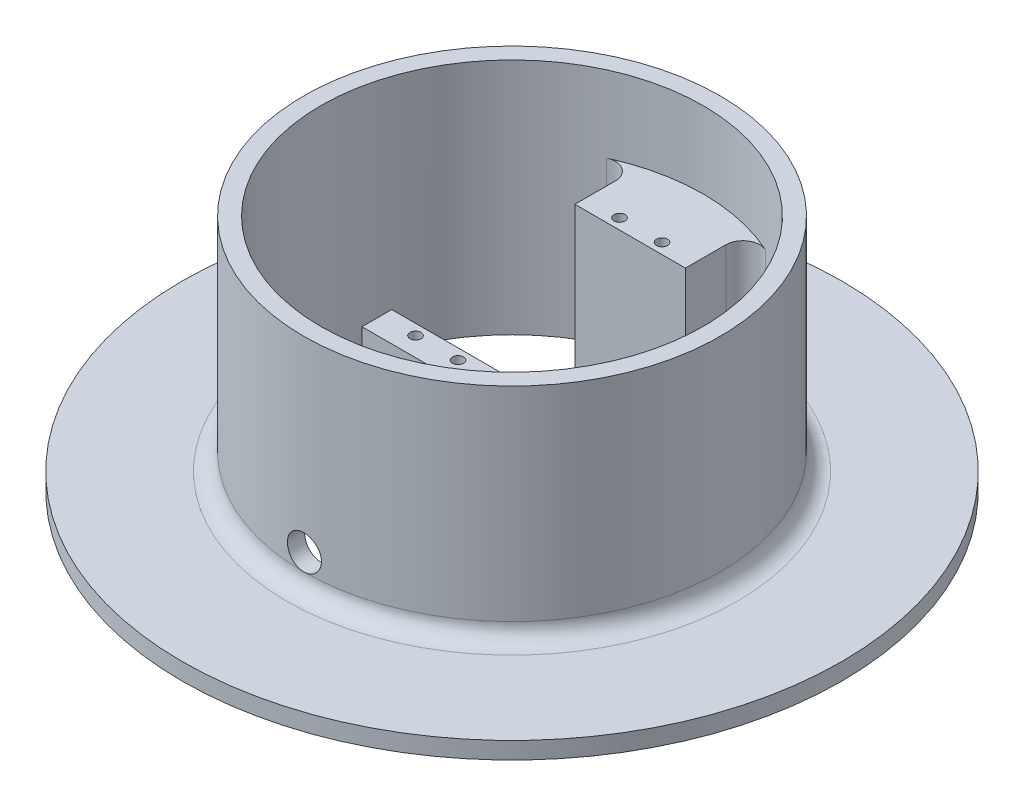
SolidWorks part; units mm, degrees
ref_plane "Front Plane" through (0, 0, 0) normal (0, 0, 1) x (1, 0, 0)
ref_plane "Top Plane" through (0, 0, 0) normal (0, 1, 0) x (1, 0, 0)
ref_plane "Right Plane" through (0, 0, 0) normal (1, 0, 0) x (0, 0, -1)
sketch "Croquis1" plane through (0, 0, 0) normal (0, 1, 0) x (1, 0, 0)
  line L0 (-10, -24.2) -> (-23.9176, -38.1176)
  line L1 (0, -45) -> (0, -24.2)
  line L2 (0, -24.2) -> (-10, -24.2)
  line L3 (0, -24.2) -> (10, -24.2)
  line L7 (0, -24.2) -> (0, -15.2)
  line L8 (0, -15.2) -> (-13.1, -15.2)
  line L9 (0, -15.2) -> (13.1, -15.2)
  line L11 (-13.1, -15.2) -> (-30.7525, -32.8525)
  line L12 (13.1, -15.2) -> (30.7525, -32.8525)
  line L13 (10, -24.2) -> (23.9176, -38.1176)
  arc A1 (-13.3684, -42.9684) -> (23.9176, -38.1176) centre (0, 0) ccw
  arc A2 (40.095, -20.4301) -> (-30.7525, -32.8525) centre (0, 0) ccw
  arc A3 (-23.9176, -38.1176) -> (23.9176, -38.1176) centre (0, 0) ccw
  arc A4 (-23.9176, -38.1176) -> (-18.1343, -41.1843) centre (0, 0) ccw
  arc A5 (30.7525, -32.8525) -> (34.7133, -28.6354) centre (0, 0) ccw
  arc A6 (30.7525, -32.8525) -> (-30.7525, -32.8525) centre (0, 0) ccw
  circle A7 centre (0, 0) radius 77.5745
  dimension "D1" = 90
  dimension "D2" = 20.8
  dimension "D3" = 10
  dimension "D4" = 10
  dimension "D6" = 9
  dimension "D7" = 13.1
  dimension "D8" = 13.1
sketch "Croquis3" plane through (0, 0, 0) normal (0, 1, 0) x (1, 0, 0)
  circle A0 centre (0, 0) radius 45
  circle A1 centre (0, 0) radius 49
  dimension "D1" = 90
  dimension "D2" = 98
extrude "Saliente-Extruir1" add sketch "Croquis3" along normal blind 56
extrude "Saliente-Extruir2" add sketch "Croquis1" along normal blind 4 contours A2 L9 L3 A1 L2 L8 region at (-75.3804, 0, 0)
sketch "Croquis5" plane through (0, 0, 0) normal (0, 1, 0) x (1, 0, 0)
  line L0 (0, -15.2) -> (0, 27.8)
  line L1 (-13.1, -15.2) -> (13.1, -15.2) construction
  line L2 (0, 27.8) -> (-13, 27.8)
  line L3 (0, 27.8) -> (13, 27.8)
  line L4 (-13, 27.8) -> (-13, 37.3095)
  line L5 (13, 27.8) -> (13, 37.3095)
  line L6 (-13.1, -15.2) -> (-13.1, -22.2)
  line L7 (-13.1, -22.2) -> (13, -22.2)
  line L8 (13, -22.2) -> (13.1, -15.2)
  line L10 (-13.1, -15.2) -> (13.1, -15.2)
  circle A0 centre (0, 0) radius 45 construction
  arc A2 (18.6585, 40.9495) -> (13, 37.3095) centre (17, 37.3095) ccw
  arc A3 (-18.6585, 40.9495) -> (-13, 37.3095) centre (-17, 37.3095) cw
  arc A4 (18.6585, 40.9495) -> (-18.6585, 40.9495) centre (0, 0) ccw
  point P14 (13, 43.0813)
  point P17 (-13, 43.0813)
  dimension "D4" = 4
  dimension "D1" = 43
  dimension "D2" = 13
  dimension "D3" = 13
  dimension "D5" = 7
extrude "Saliente-Extruir3" add sketch "Croquis5" along normal blind 38 contours A2 A4 A3 L4 L2 L3 L5 | L10 L6 L7 L8 region at (0, 0, -36.2791) region at (-0.025, 0, 18.6978)
ref_plane "Plano1" through (0, 0, 15) normal (0, 0, 1) x (1, 0, 0)
sketch "Croquis6" plane through (0, 0, 15) normal (0, 0, 1) x (1, 0, 0)
  line L0 (0, 0) -> (0, 5)
  line L1 (0, 5) -> (-5, 5)
  line L2 (-5, 5) -> (-5, 29)
  line L3 (-5, 29) -> (-2.4928, 29)
  line L4 (-2.4928, 29) -> (5, 29)
  line L5 (5, 29) -> (5, 5)
  line L6 (5, 5) -> (0, 5)
  dimension "D1" = 5
  dimension "D2" = 5
  dimension "D3" = 5
  dimension "D4" = 24
  dimension "D5" = 24
extrude "Cortar-Extruir1" cut sketch "Croquis6" along normal blind 8 contours L6 L5 L4 L3 L2 L1 region at (0, 17, 15)
sketch "Croquis7" plane through (0, 0, 15) normal (0, 0, 1) x (1, 0, 0)
  line L0 (0, 0) -> (0, 12)
  circle A0 centre (0, 12) radius 4
  dimension "D1" = 12
extrude "Cortar-Extruir2" cut sketch "Croquis7" along normal blind 42 contours A0 region at (2.7484, 9.2516, 15)
fillet "Redondeo1" radius 4 1 edges at (0, 4, 49)
fillet "Redondeo2" radius 1 3 edges at (-0.05, 4, 22.2) (13.05, 4, 18.7) (-13.1, 4, 18.7)
ref_plane "Plano2" through (0, 60, 0) normal (0, 1, 0) x (1, 0, 0)
sketch "Croquis8" plane through (0, 60, 0) normal (0, 1, 0) x (1, 0, 0)
  line L0 (0, -15.2) -> (0, -17.626)
  line L1 (-13.1, -15.2) -> (13.1, -15.2) construction
  line L2 (0, -15.2) -> (-5, -15.2)
  line L3 (-5, -15.2) -> (-5, -17.7)
  line L4 (0, -15.2) -> (0, 27.8)
  line L5 (13, 27.8) -> (-13, 27.8) construction
  line L6 (0, 6.3) -> (-4.3875, 6.3)
  circle A0 centre (-5, -17.7) radius 1.3
  circle A1 centre (5, -17.7) radius 1.3
  circle A2 centre (5, 30.3) radius 1.3
  circle A3 centre (-5, 30.3) radius 1.3
  dimension "D3" = 2.6
  dimension "D1" = 5
  dimension "D2" = 2.5
extrude "Cortar-Extruir3" cut sketch "Croquis8" against normal blind 30.8 contours A3 | A2 | A0 | A1
